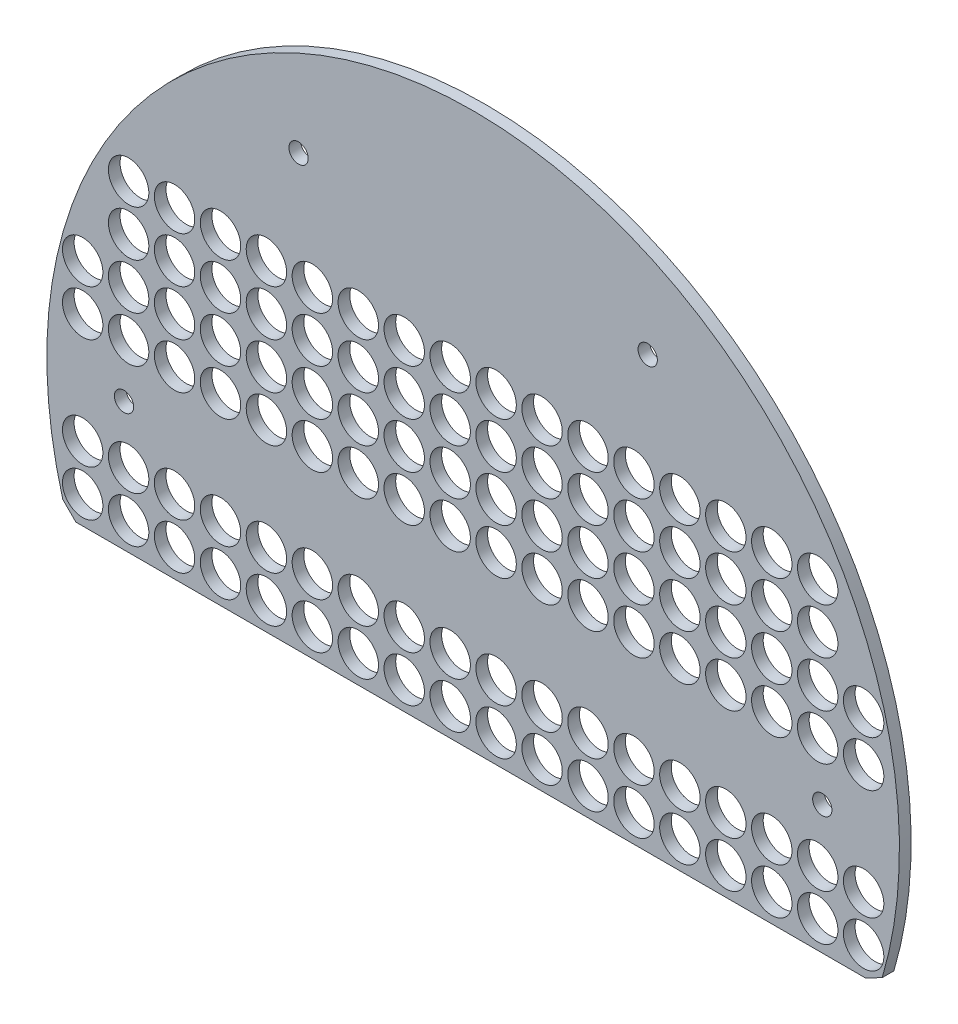
SolidWorks part; units mm, degrees
ref_plane "Front Plane" through (0, 0, 0) normal (0, 0, 1) x (1, 0, 0)
ref_plane "Top Plane" through (0, 0, 0) normal (0, 1, 0) x (1, 0, 0)
ref_plane "Right Plane" through (0, 0, 0) normal (1, 0, 0) x (0, 0, -1)
sketch "Sketch1" plane through (0, 0, 0) normal (0, 0, 1) x (1, 0, 0)
  line L0 (-221.1877, 70) -> (221.1877, 70)
  arc A0 (-221.1877, 70) -> (221.1877, 70) centre (0, 0) ccw
  dimension "D1" = 464
  dimension "D2" = 70
extrude "Boss-Extrude1" add sketch "Sketch1" along normal blind 6.35
chamfer "Chamfer1" distance 5 angle 45 2 edges at (-221.1877, 70, 3.175) (221.1877, 70, 3.175) first distance on face at (0, 70, 3.175) first distance on face at (0, -81, 3.175)
sketch "Sketch2" plane through (0, 0, 6.35) normal (0, 0, 1) x (1, 0, 0)
  circle A1 centre (-190, 0) radius 5.25
  circle A4 centre (190, 0) radius 5.25
  circle A5 centre (95, -164.5448) radius 5.25
  circle A6 centre (-95, -164.5448) radius 5.25
  arc A7 (-189.9275, 5.2495) -> (189.9275, 5.2495) centre (0, 0) ccw construction
  arc A8 (-99.5099, 161.8573) -> (-90.4175, 167.1068) centre (-95, 164.5448) ccw [skipped]
  arc A9 (99.5099, 161.8573) -> (90.4175, 167.1068) centre (95, 164.5448) ccw [skipped]
  point P18 (0, 0)
  dimension "D1" = 190
  dimension "D2" = 10.5
  dimension "D4" = 190
  dimension "D5" = 164.5448
  dimension "D6" = 95
  dimension "D3" = 6
extrude "Cut-Extrude1" cut sketch "Sketch2" against normal through all
sketch "Sketch3" plane through (0, 0, 6.35) normal (0, 0, 1) x (1, 0, 0)
  line L0 (0, 140.2547) -> (0, -298.7075) construction
  line L1 (-353.8302, 0) -> (406.1509, 0) construction
  circle A0 centre (12.5, -30) radius 11
  circle A1 centre (12.5, -55) radius 11
  circle A2 centre (12.5, -80) radius 11
  circle A3 centre (12.5, -105) radius 11
  circle A4 centre (37.5, -30) radius 11
  circle A5 centre (37.5, -55) radius 11
  circle A6 centre (62.5, -30) radius 11
  circle A7 centre (62.5, -55) radius 11
  circle A8 centre (87.5, -30) radius 11
  circle A9 centre (87.5, -55) radius 11
  circle A10 centre (112.5, -30) radius 11
  circle A11 centre (112.5, -55) radius 11
  circle A12 centre (137.5, -30) radius 11
  circle A13 centre (137.5, -55) radius 11
  circle A14 centre (162.5, -30) radius 11
  circle A15 centre (162.5, -55) radius 11
  circle A16 centre (187.5, -30) radius 11
  circle A17 centre (187.5, -55) radius 11
  circle A18 centre (212.5, -30) radius 11
  circle A19 centre (212.5, -55) radius 11
  circle A20 centre (37.5, -80) radius 11
  circle A21 centre (37.5, -105) radius 11
  circle A22 centre (62.5, -80) radius 11
  circle A23 centre (62.5, -105) radius 11
  circle A24 centre (87.5, -80) radius 11
  circle A25 centre (87.5, -105) radius 11
  circle A26 centre (112.5, -80) radius 11
  circle A27 centre (112.5, -105) radius 11
  circle A28 centre (137.5, -80) radius 11
  circle A29 centre (137.5, -105) radius 11
  circle A30 centre (162.5, -80) radius 11
  circle A31 centre (162.5, -105) radius 11
  circle A32 centre (187.5, -80) radius 11
  circle A33 centre (187.5, -105) radius 11
  circle A34 centre (12.5, 30) radius 11
  circle A35 centre (12.5, 55) radius 11
  circle A36 centre (37.5, 55) radius 11
  circle A37 centre (37.5, 30) radius 11
  circle A38 centre (62.5, 55) radius 11
  circle A39 centre (62.5, 30) radius 11
  circle A40 centre (87.5, 55) radius 11
  circle A41 centre (87.5, 30) radius 11
  circle A42 centre (112.5, 55) radius 11
  circle A43 centre (112.5, 30) radius 11
  circle A44 centre (137.5, 55) radius 11
  circle A45 centre (137.5, 30) radius 11
  circle A46 centre (162.5, 55) radius 11
  circle A47 centre (162.5, 30) radius 11
  circle A48 centre (187.5, 55) radius 11
  circle A49 centre (187.5, 30) radius 11
  circle A50 centre (212.5, 55) radius 11
  circle A51 centre (212.5, 30) radius 11
  dimension "D1" = 22
  dimension "D2" = 22
  dimension "D3" = 22
  dimension "D4" = 22
  dimension "D14" = 22
  dimension "D15" = 22
  dimension "D5" = 12.5
  dimension "D6" = 30
  dimension "D7" = 55
  dimension "D8" = 80
  dimension "D9" = 105
  dimension "D12" = 37.5
  dimension "D13" = 37.5
  dimension "D16" = 30
  dimension "D17" = 55
  dimension "D19" = 37.5
  dimension "D10" = 9
  dimension "D11" = 8
  dimension "D18" = 9
extrude "Cut-Extrude2" cut sketch "Sketch3" against normal through all
mirror "Mirror2" about plane through (0, 0, 0) normal (1, 0, 0) of "Cut-Extrude2"
move or copy body "Body-Move/Copy1" bodies to move or copy 105 copy no rotation origin (0, 0, 0) rotation axis (1, 0, 0) rotation angle 180
